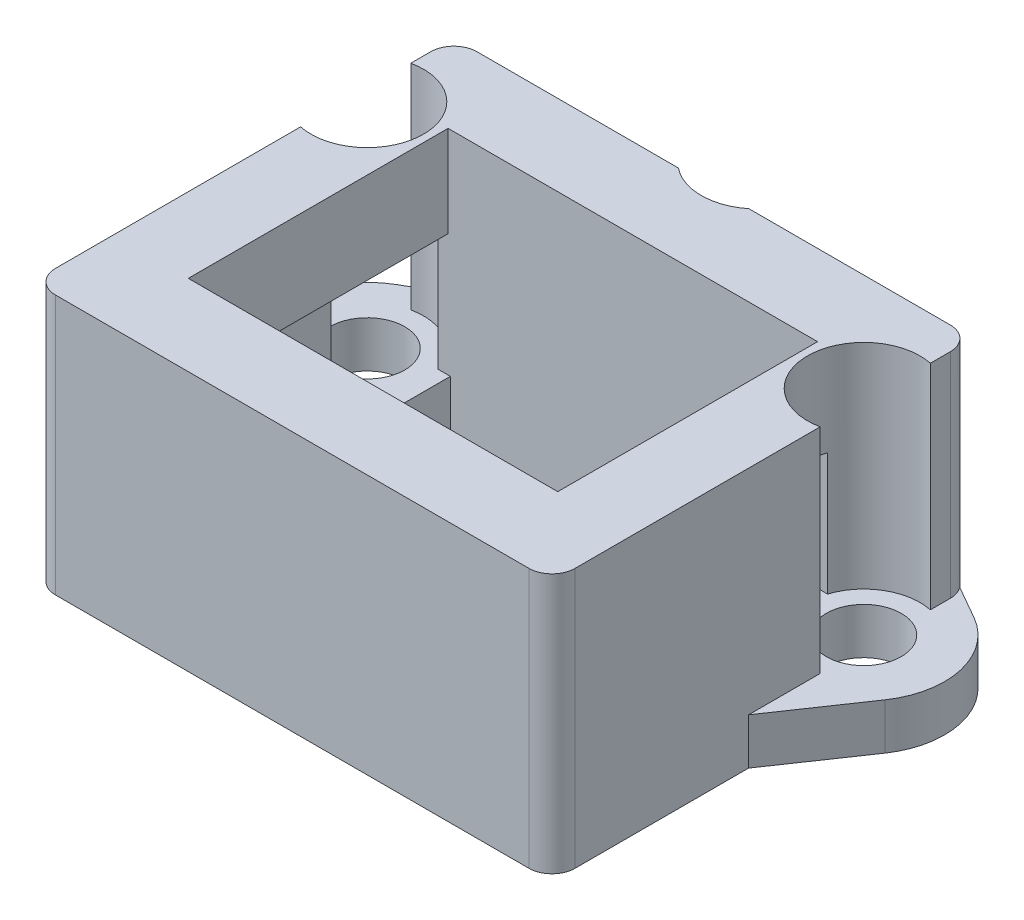
SolidWorks part; units mm, degrees
ref_plane "Front Plane" through (0, 0, 0) normal (0, 0, 1) x (1, 0, 0)
ref_plane "Top Plane" through (0, 0, 0) normal (0, 1, 0) x (1, 0, 0)
ref_plane "Right Plane" through (0, 0, 0) normal (1, 0, 0) x (0, 0, -1)
sketch "Sketch2" plane through (0, 0, 0) normal (0, 1, 0) x (1, 0, 0)
  line L1 (-16, 11.25) -> (16, 11.25)
  line L2 (-16, 11.25) -> (-16, -11.25)
  line L3 (-16, -11.25) -> (16, -11.25)
  line L4 (16, 11.25) -> (16, -11.25)
  line L5 (-16, 11.25) -> (16, -11.25) construction
  line L6 (-16, -11.25) -> (16, 11.25) construction
  line L7 (-22.5, 18.25) -> (22.5, 18.25)
  line L8 (-22.5, 18.25) -> (-22.5, -18.25)
  line L9 (-22.5, -18.25) -> (22.5, -18.25)
  line L10 (22.5, 18.25) -> (22.5, -18.25)
  line L11 (-22.5, 18.25) -> (22.5, -18.25) construction
  line L12 (-22.5, -18.25) -> (22.5, 18.25) construction
  point P0 (0, 0)
  point P5 (0, 0)
  point P10 (-19.6604, 37.5642)
  dimension "D1" = 45
  dimension "D2" = 32
  dimension "D3" = 22.5
  dimension "D4" = 7
extrude "Boss-Extrude2" add sketch "Sketch2" against normal blind 22.5
ref_plane "Plane1" through (0, -7.9, 0) normal (0, 1, 0) x (1, 0, 0)
ref_plane "Plane2" through (0, -22.5, 0) normal (0, -1, 0) x (-1, 0, 0)
sketch "Sketch3" plane through (0, -7.9, 0) normal (0, 1, 0) x (1, 0, 0)
  line L0 (-16, -11.25) -> (16, -11.25) construction
  line L1 (-20, -11.25) -> (20, -11.25)
  line L2 (-20, -11.25) -> (-20, 11.25)
  line L3 (-20, 11.25) -> (20, 11.25)
  line L4 (20, -11.25) -> (20, 11.25)
  line L5 (-20, -11.25) -> (20, 11.25) construction
  line L6 (-20, 11.25) -> (20, -11.25) construction
  point P0 (0, 0)
  dimension "D1" = 40
extrude "Cut-Extrude1" cut sketch "Sketch3" against normal through all
sketch "Sketch5" plane through (0, -22.5, 0) normal (0, -1, 0) x (-1, 0, 0)
  line L0 (-21.5, 9.75) -> (21.5, 9.75) construction
  line L1 (0, 22.05) -> (0, 9.75) construction
  line L2 (-24.976, 15.826) -> (-3.476, 28.126)
  line L3 (-15.8, 11.25) -> (15.8, 11.25)
  line L4 (15.8, 11.25) -> (15.8, -2.156)
  line L5 (3.476, 28.126) -> (24.976, 15.826)
  line L6 (-15.8, 11.25) -> (-15.8, -2.25)
  line L7 (-15.8, -2.25) -> (-21.8, -2.25)
  line L8 (-21.8, -2.25) -> (-27.2868, 5.8113)
  line L9 (15.8, -2.156) -> (21.8, -2.156)
  line L10 (21.8, -2.156) -> (27.2651, 5.7797)
  line L13 (-16, 11.25) -> (16, 11.25) construction
  line L14 (0, 12.375) -> (0, -12.375) construction
  circle A0 centre (21.5, 9.75) radius 3.25
  circle A1 centre (-21.5, 9.75) radius 3.25
  circle A2 centre (0, 22.05) radius 3.25
  arc A3 (-3.476, 28.126) -> (3.476, 28.126) centre (0, 22.05) cw
  arc A4 (-27.2868, 5.8113) -> (-24.976, 15.826) centre (-21.5, 9.75) cw
  arc A5 (27.2651, 5.7797) -> (24.976, 15.826) centre (21.5, 9.75) ccw
  point P7 (-35.6561, -8.2144)
  point P21 (0, 0)
  point P23 (-34.61, 9.6812)
  point P24 (0, 9.75)
  point P25 (0, 0)
  point P28 (0, 11.25)
  dimension "D5" = 7
  dimension "D6" = 7
  dimension "D7" = 7
  dimension "D1" = 31.6
  dimension "D2" = 12.3
  dimension "D3" = 43
  dimension "D4" = 13.5
  dimension "D8" = 6
extrude "Boss-Extrude3" add sketch "Sketch5" against normal blind 4
sketch "Sketch7" plane through (0, -22.5, 0) normal (0, -1, 0) x (-1, 0, 0)
  circle A0 centre (-21.5, 9.75) radius 3.25
  circle A1 centre (0, 22.05) radius 3.25
  circle A2 centre (21.5, 9.75) radius 3.25
  arc A3 (22.5, 6.6577) -> (22.5, 12.8423) centre (21.5, 9.75) ccw construction
  arc A4 (-22.5, 12.8423) -> (-22.5, 6.6577) centre (-21.5, 9.75) ccw construction
  circle A5 centre (0, 22.05) radius 3.25 construction
  dimension "D1" = 6.5
extrude "Cut-Extrude2" cut sketch "Sketch7" against normal through all
sketch "Sketch8" plane through (0, 0, 0) normal (0, 1, 0) x (1, 0, 0)
  circle A0 centre (0, 22.05) radius 4.875
  circle A1 centre (-21.5, 9.75) radius 4.875
  circle A2 centre (21.5, 9.75) radius 4.875
  circle A3 centre (0, 22.05) radius 3.25 construction
  arc A4 (22.5, 6.6577) -> (22.5, 12.8423) centre (21.5, 9.75) ccw construction
  arc A5 (-22.5, 12.8423) -> (-22.5, 6.6577) centre (-21.5, 9.75) ccw construction
  dimension "D1" = 9.75
extrude "Cut-Extrude3" cut sketch "Sketch8" against normal up to surface (18.5 mm away) up to face at (-24.4493, -18.5, -9.6185)
fillet "Fillet1" radius 2 4 edges at (-22.5, -11.25, -18.25) (22.5, -11.25, -18.25) (-22.5, -11.25, 18.25) (22.5, -11.25, 18.25)
